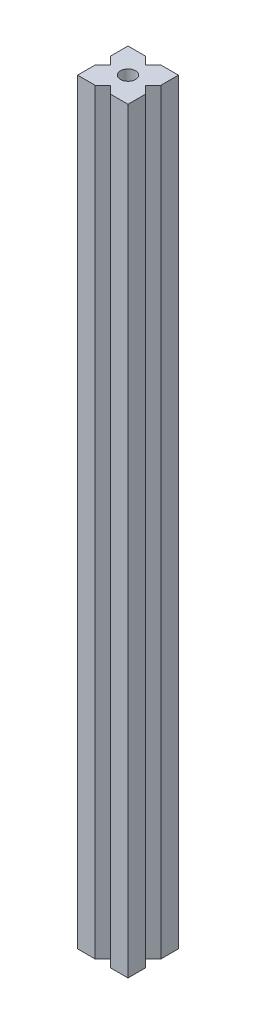
SolidWorks part; units mm, degrees
ref_plane "Front" through (0, 0, 0) normal (0, 0, 1) x (1, 0, 0)
ref_plane "Top" through (0, 0, 0) normal (0, 1, 0) x (1, 0, 0)
ref_plane "Right" through (0, 0, 0) normal (1, 0, 0) x (0, 0, -1)
sketch "Skizze1" plane through (0, 0, 0) normal (0, 1, 0) x (1, 0, 0)
  line L1 (0, 0) -> (20, 0)
  line L2 (0, 0) -> (0, 20)
  line L3 (0, 20) -> (20, 20)
  line L4 (20, 0) -> (20, 20)
  dimension "D1" = 20
extrude "Aufsatz-Linear austragen1" add sketch "Skizze1" along normal blind 300
sketch "Skizze2" plane through (0, 300, 0) normal (0, 1, 0) x (1, 0, 0)
  line L0 (10, 20) -> (10, 0) construction
  line L1 (0, 10) -> (20, 10) construction
  line L2 (7, 20) -> (10, 17)
  line L3 (13, 20) -> (10, 17)
  line L4 (10, 10) -> (20, 20) construction
  line L5 (7, 20) -> (13, 20)
  line L6 (20, 13) -> (17, 10)
  line L7 (20, 7) -> (17, 10)
  line L8 (20, 7) -> (20, 13)
  line L9 (0, 7) -> (0, 13)
  line L10 (0, 7) -> (3, 10)
  line L11 (0, 13) -> (3, 10)
  line L12 (7, 0) -> (13, 0)
  line L13 (13, 0) -> (10, 3)
  line L14 (7, 0) -> (10, 3)
  line L15 (20, 20) -> (0, 20) construction
  line L16 (20, 0) -> (20, 20) construction
  line L17 (0, 0) -> (20, 0) construction
  dimension "D1" = 3
  dimension "D2" = 3
extrude "Schnitt-Linear austragen1" cut sketch "Skizze2" against normal through all
ref_plane "Ebene1" through (10, 0, 0) normal (1, 0, 0) x (0, 0, -1)
sketch "Skizze3" plane through (0, 300, 0) normal (0, 1, 0) x (1, 0, 0)
  line L0 (3, 10) -> (17, 10) construction
  circle A0 centre (10, 10) radius 3
  dimension "D1" = 6
extrude "Schnitt-Linear austragen2" cut sketch "Skizze3" against normal through all
ref_plane "Plane1" through (0, 150, 0) normal (0, 1, 0) x (1, 0, 0)
ref_plane "Plane2" through (0, 0, -10) normal (0, 0, -1) x (-1, 0, 0)
